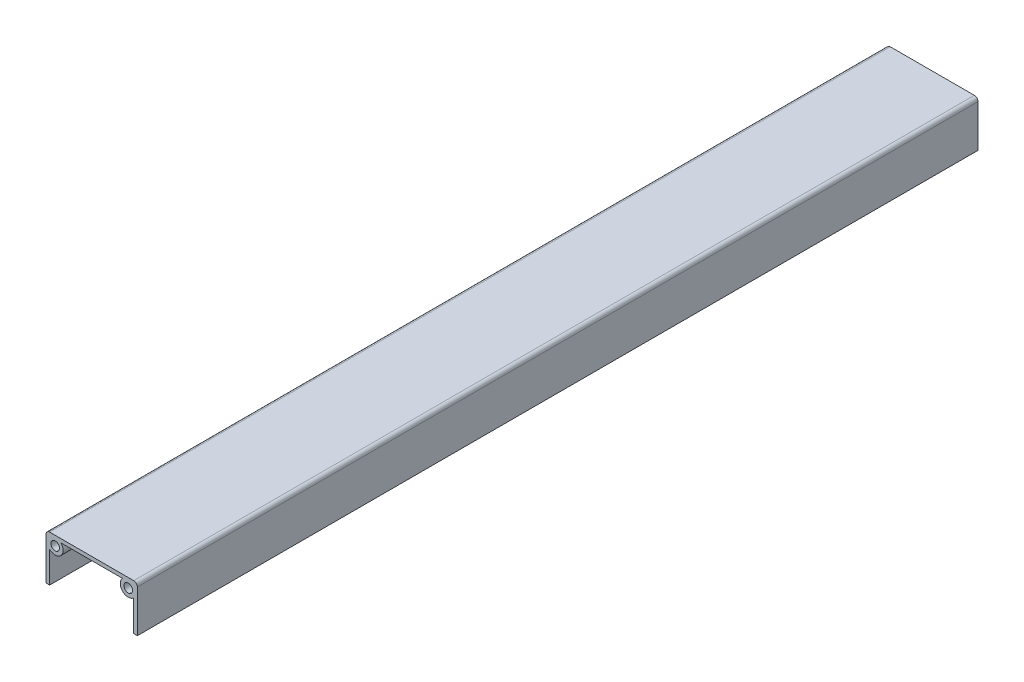
SolidWorks part; units mm, degrees
ref_plane "Front Plane" through (0, 0, 0) normal (0, 0, 1) x (1, 0, 0)
ref_plane "Top Plane" through (0, 0, 0) normal (0, 1, 0) x (1, 0, 0)
ref_plane "Right Plane" through (0, 0, 0) normal (1, 0, 0) x (0, 0, -1)
sketch "Sketch1" plane through (0, 0, 0) normal (0, 0, 1) x (1, 0, 0)
  line L0 (0, 31.75) -> (0, -31.75) construction
  line L1 (-31.75, -31.75) -> (31.75, -31.75)
  line L2 (-31.75, -31.75) -> (-31.75, 31.75)
  line L3 (-31.75, 31.75) -> (31.75, 31.75)
  line L4 (31.75, -31.75) -> (31.75, 31.75)
  line L5 (-31.75, -31.75) -> (31.75, 31.75) construction
  line L6 (-31.75, 31.75) -> (31.75, -31.75) construction
  line L7 (-31.75, 0) -> (31.75, 0) construction
  circle A0 centre (-25.4, 25.4) radius 3
  circle A1 centre (25.4, -25.4) radius 3
  circle A2 centre (-25.4, -25.4) radius 3
  circle A3 centre (25.4, 25.4) radius 3
  point P0 (0, 0)
  dimension "D3" = 6
  dimension "D9" = 50.8
  dimension "D4" = 50.8
  dimension "D1" = 63.5
  dimension "D2" = 63.5
  dimension "D5" = 6.35
extrude "Boss-Extrude1" add sketch "Sketch1" along normal mid plane 584.2
fillet "Fillet1" radius 2.54 4 edges at (-31.75, -31.75, 0) (31.75, -31.75, 0) (-31.75, 31.75, 0) (31.75, 31.75, 0)
shell "Shell1" thickness 2.54 removed face at (-28.4, -25.4, -292.1) removed face at (0, 0, 292.1)
sketch "Sketch3" plane through (0, 0, 292.1) normal (0, 0, 1) x (1, 0, 0)
  line L1 (-31.75, 29.21) -> (-31.75, -29.21) construction
  line L2 (-31.75, -0.1289) -> (31.9153, -0.1289)
  line L3 (-31.75, -0.1289) -> (-31.75, -31.8789)
  line L4 (-31.75, -31.8789) -> (31.9153, -31.8789)
  line L5 (31.9153, -0.1289) -> (31.9153, -31.8789)
  dimension "D1" = 31.75
extrude "Cut-Extrude2" cut sketch "Sketch3" against normal through all
